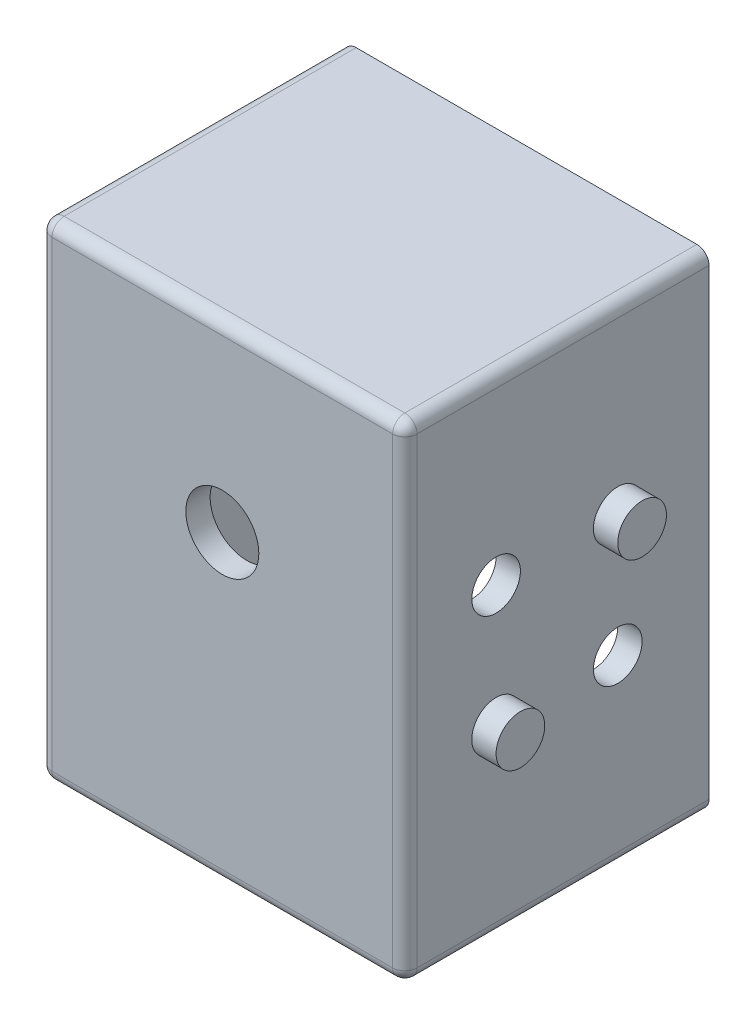
SolidWorks part; units mm, degrees
ref_plane "Front Plane" through (0, 0, 0) normal (0, 0, 1) x (1, 0, 0)
ref_plane "Top Plane" through (0, 0, 0) normal (0, 1, 0) x (1, 0, 0)
ref_plane "Right Plane" through (0, 0, 0) normal (1, 0, 0) x (0, 0, -1)
sketch "Sketch2" plane through (0, 0, 0) normal (0, 0, 1) x (1, 0, 0)
  line L1 (0, 0) -> (30, 0)
  line L2 (0, 0) -> (0, 40)
  line L3 (0, 40) -> (30, 40)
  line L4 (30, 0) -> (30, 40)
  dimension "D1" = 30
  dimension "D2" = 40
extrude "Boss-Extrude2" add sketch "Sketch2" along normal blind 25 contours L3 L4 L1 L2
fillet "Fillet2" radius 1 4 edges at (15, 0, 25) (30, 20, 25) (0, 20, 25) (15, 40, 25)
fillet "Fillet3" radius 1 8 edges at (29.7071, 0.2929, 24.7071) (0.2929, 0.2929, 24.7071) (0.2929, 39.7071, 24.7071) (29.7071, 39.7071, 24.7071) (30, 0, 12) (0, 0, 12) (0, 40, 12) (30, 40, 12)
shell "Shell1" thickness 2 removed face at (15, 20, 0)
fillet "Fillet4" radius 1 4 edges at (15, 38, 23) (15, 2, 23) (28, 20, 23) (2, 20, 23)
sketch "Sketch4" plane through (0, 0, 25) normal (0, 0, 1) x (1, 0, 0)
  line L1 (30, 39) -> (30, 1) construction
  line L3 (1, 40) -> (29, 40) construction
  circle A0 centre (15, 25) radius 3
  dimension "D1" = 15
  dimension "D2" = 15
sketch "Sketch5" plane through (0, 0, 0) normal (0, -1, 0) x (1, 0, 0)
  line L1 (30, 24) -> (30, 0) construction
  line L3 (1, 0) -> (29, 0) construction
  line L4 (0, 0) -> (0, 24) construction
  line L5 (1, 25) -> (29, 25) construction
  circle A0 centre (10, 17.5) radius 2
  circle A1 centre (20, 7.5) radius 2
  circle A2 centre (20, 17.5) radius 2
  circle A3 centre (10, 7.5) radius 2
  dimension "D1" = 10
  dimension "D3" = 10
  dimension "D5" = 7.5
  dimension "D2" = 10
  dimension "D4" = 7.5
  dimension "D6" = 7.5
  dimension "D7" = 7.5
  dimension "D8" = 10
extrude "Cut-Extrude10" cut sketch "Sketch5" against normal blind 2 contours A3 | A2
sketch "Sketch7" plane through (0, 0, 0) normal (0, -1, 0) x (-1, 0, 0)
  line L0 (-30, -24) -> (-30, 0) construction
  line L1 (-1, 0) -> (-29, 0) construction
  line L2 (0, 0) -> (0, -24) construction
  line L3 (-1, -25) -> (-29, -25) construction
  circle A0 centre (-10, -17.5) radius 2
  circle A1 centre (-20, -7.5) radius 2
  dimension "D1" = 10
  dimension "D2" = 7.5
  dimension "D3" = 10
  dimension "D4" = 7.5
extrude "Boss-Extrude3" add sketch "Sketch7" along normal blind 2 contours A1 | A0
extrude "Cut-Extrude11" cut sketch "Sketch4" against normal blind 2 contours A0
sketch "Sketch8" plane through (30, 0, 0) normal (1, 0, 0) x (0, 0, -1)
  line L0 (0, 1) -> (0, 39) construction
  line L1 (-24, 40) -> (0, 40) construction
  line L2 (0, 0) -> (-24, 0) construction
  line L3 (-25, 1) -> (-25, 39) construction
  circle A0 centre (-7.5, 25) radius 2
  circle A1 centre (-7.5, 15) radius 2
  circle A2 centre (-17.5, 15) radius 2
  circle A3 centre (-17.5, 25) radius 2
  dimension "D1" = 7.5
  dimension "D2" = 7.5
  dimension "D3" = 15
  dimension "D4" = 15
  dimension "D5" = 7.5
  dimension "D6" = 7.5
  dimension "D7" = 15
  dimension "D8" = 15
extrude "Boss-Extrude5" add sketch "Sketch8" along normal blind 2 contours A2 | A0
sketch "Sketch9" plane through (30, 0, 0) normal (1, 0, 0) x (0, 0, -1)
  line L0 (0, 1) -> (0, 39) construction
  line L1 (0, 0) -> (-24, 0) construction
  line L2 (-25, 1) -> (-25, 39) construction
  line L3 (-24, 40) -> (0, 40) construction
  circle A0 centre (-7.5, 15) radius 2
  circle A1 centre (-17.5, 25) radius 2
  dimension "D1" = 7.5
  dimension "D2" = 15
  dimension "D3" = 7.5
  dimension "D4" = 15
extrude "Cut-Extrude12" cut sketch "Sketch9" against normal blind 2 contours A1 | A0
sketch "Sketch10" plane through (0, 0, 0) normal (-1, 0, 0) x (0, 0, 1)
  line L0 (0, 40) -> (24, 40) construction
  line L1 (0, 1) -> (0, 39) construction
  line L2 (24, 1) -> (24, 39) construction
  line L3 (24, 0) -> (0, 0) construction
  circle A0 centre (7.5, 25) radius 2
  circle A1 centre (16.5, 15) radius 2
  dimension "D1" = 15
  dimension "D2" = 7.5
  dimension "D3" = 7.5
  dimension "D4" = 15
extrude "Cut-Extrude13" cut sketch "Sketch10" against normal blind 2 contours A1 | A0
sketch "Sketch11" plane through (0, 0, 0) normal (-1, 0, 0) x (0, 0, 1)
  line L0 (24, 1) -> (24, 39) construction
  line L1 (0, 40) -> (24, 40) construction
  line L2 (0, 1) -> (0, 39) construction
  line L3 (24, 0) -> (0, 0) construction
  circle A0 centre (16.5, 25) radius 2
  circle A1 centre (7.5, 15) radius 2
  dimension "D1" = 7.5
  dimension "D2" = 15
  dimension "D3" = 7.5
  dimension "D4" = 15
extrude "Boss-Extrude6" add sketch "Sketch11" along normal blind 2
